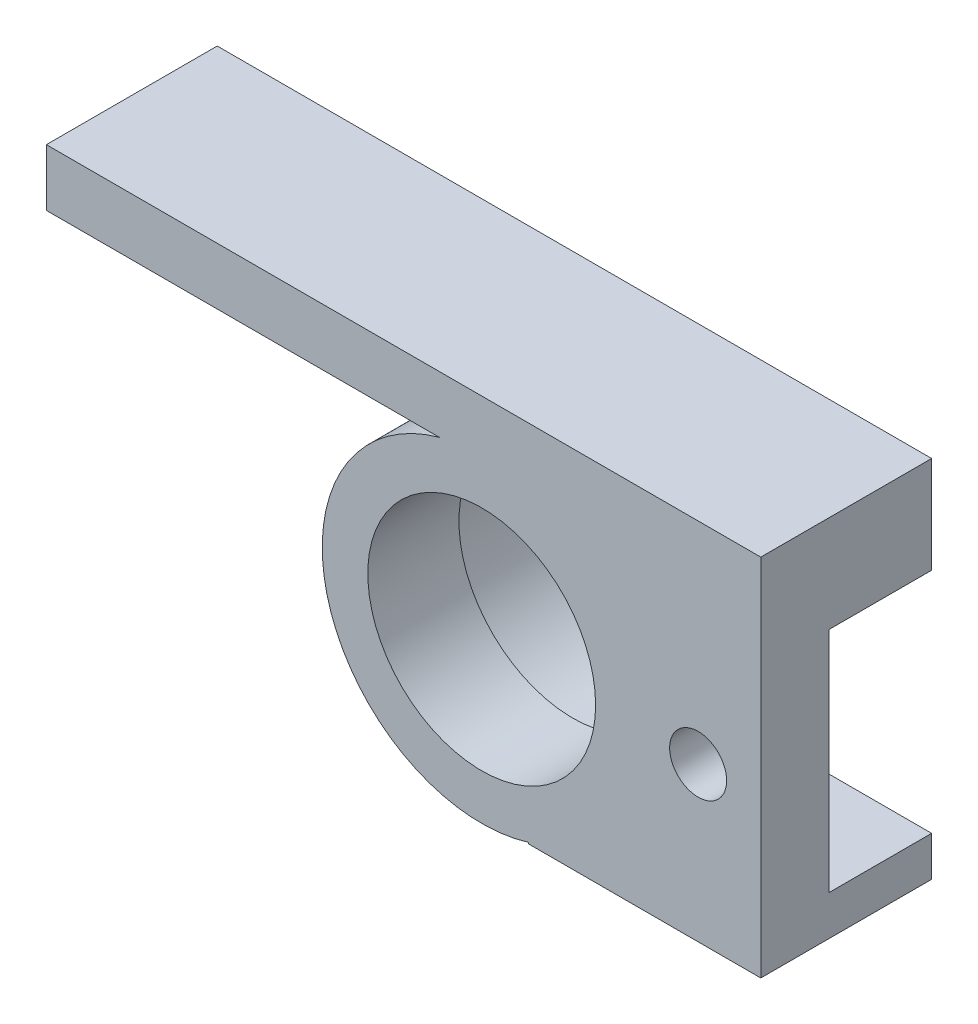
SolidWorks part; units mm, degrees
ref_plane "前视基准面" through (0, 0, 0) normal (0, 0, 1) x (1, 0, 0)
ref_plane "上视基准面" through (0, 0, 0) normal (0, 1, 0) x (1, 0, 0)
ref_plane "右视基准面" through (0, 0, 0) normal (1, 0, 0) x (0, 0, -1)
sketch "草图1" plane through (0, 0, 0) normal (0, 0, 1) x (1, 0, 0)
  line L1 (20, -10) -> (-20, -10)
  line L2 (20, -10) -> (20, 10)
  line L3 (20, 10) -> (-20, 10)
  line L4 (-20, -10) -> (-20, 10)
  line L5 (20, -10) -> (-20, 10) construction
  line L6 (20, 10) -> (-20, -10) construction
  point P0 (0, 0)
  dimension "D1" = 40
  dimension "D2" = 20
extrude "凸台-拉伸1" add sketch "草图1" along normal blind 6
sketch "草图2" plane through (0, 0, 6) normal (0, 0, 1) x (1, 0, 0)
  line L0 (20, -10) -> (20, 10) construction
  circle A0 centre (10, 0) radius 2.5
  circle A1 centre (-1, 0) radius 2.5
  circle A2 centre (-12, 0) radius 2.5
  dimension "D1" = 10
  dimension "D2" = 5
  dimension "D3" = 3
extrude "切除-拉伸1" cut sketch "草图2" against normal through all
sketch "草图3" plane through (0, 0, 6) normal (0, 0, 1) x (1, 0, 0)
  line L0 (20, 13.5) -> (20, 10)
  line L1 (20, -13.5) -> (-26.894, -13.5)
  line L3 (20, 13.5) -> (-26.894, 13.5)
  line L4 (-20, 10) -> (-20, -10)
  line L5 (-20, -10) -> (20, -10)
  line L6 (20, -10) -> (20, 10)
  line L7 (20, 10) -> (-20, 10)
  line L8 (-20, 10) -> (-20, -10)
  line L9 (-20, -10) -> (20, -10)
  line L10 (20, -10) -> (20, 10)
  line L11 (20, 10) -> (-20, 10)
  line L12 (-26.894, -13.5) -> (-26.894, 13.5)
  line L13 (20, -10.0394) -> (-26.894, 13.5) construction
  line L14 (20, 10.0394) -> (-26.894, -13.5) construction
  line L15 (20, -10) -> (20, -13.5)
  circle A0 centre (-31, 0) radius 11
  circle A1 centre (-31, 0) radius 14
  point P2 (0, 0)
  line M10 (-20, 10) -> (-20, -10)
  line M11 (-20, -10) -> (20, -10)
  line M13 (20, 10) -> (-20, 10)
  dimension "D3" = 22
  dimension "D4" = 28
  dimension "D2" = 3.5
  dimension "D1" = 0
extrude "凸台-拉伸2" add sketch "草图3" against normal blind 15 contours L3 A1 L1 L12 A0 | A1 L1 L15 M11 M10 | L1 A1 L8 A0 L12 | L8 A1 L3 L12 A0 | L8 A1 | A1 L0 L3 M10 M13 region at (-1.9449, 11.7771, 6) region at (-1.9449, -11.7771, 6) region at (-23.0173, 9.0328, 6) region at (-27.2274, 11.7946, 6) region at (-18.7882, 0, 6) region at (-23.0173, -9.0328, 6)
sketch "草图5" plane through (0, 0, 6) normal (0, 0, 1) x (1, 0, 0)
  circle A0 centre (-31, 0) radius 10
  circle A1 centre (-31, 0) radius 11 construction
  circle A2 centre (-31, 0) radius 11
  dimension "D1" = 20
extrude "凸台-拉伸3" add sketch "草图5" against normal blind 8
sketch "草图6" plane through (0, 0, 6) normal (0, 0, 1) x (1, 0, 0)
  circle A0 centre (-31, 0) radius 8.5
  circle A1 centre (-31, 0) radius 10 construction
  circle A2 centre (-31, 0) radius 10
  dimension "D1" = 17
sketch "草图7" plane through (0, 13.5, 0) normal (0, 1, 0) x (1, 0, 0)
  circle A0 centre (-17.1666, 1.953) radius 2.6594
sketch "草图8" plane through (20, 0, 0) normal (1, 0, 0) x (0, 0, -1)
  line L1 (-6, 13.5) -> (9, 13.5)
  line L2 (-6, 13.5) -> (-6, 18.5)
  line L3 (-6, 18.5) -> (9, 18.5)
  line L4 (9, 13.5) -> (9, 18.5)
  dimension "D1" = 5
extrude "凸台-拉伸4" add sketch "草图8" against normal blind 500
sketch "草图9" plane through (0, 0, -9) normal (0, 0, -1) x (-1, 0, 0)
  line L1 (24.4567, 15.8334) -> (28.494, 15.8334)
  line L2 (24.4567, 15.8334) -> (24.4567, 12.469)
  line L3 (24.4567, 12.469) -> (28.494, 12.469)
  line L4 (28.494, 15.8334) -> (28.494, 12.469)
extrude "凸台-拉伸5" add sketch "草图9" against normal through all
sketch "草图10" plane through (0, 0, 6) normal (0, 0, 1) x (1, 0, 0)
  line L0 (-12, 0) -> (-1, 0) construction
  line L1 (-6.5, 0) -> (-6.5, 18.5) construction
  line L2 (-480, 18.5) -> (20, 18.5) construction
  line L4 (-6.5, 18.5) -> (20, 18.5)
  line L5 (-6.5, 18.5) -> (-6.5, -13.5)
  line L6 (-6.5, -13.5) -> (20, -13.5)
  line L7 (20, 18.5) -> (20, -13.5)
extrude "切除-拉伸2" cut sketch "草图10" against normal through all
sketch "草图11" plane through (0, 18.5, 0) normal (0, 1, 0) x (1, 0, 0)
  line L0 (-69.2198, 9) -> (-69.2198, -6.0139)
  line L1 (-480, 9) -> (-6.5, 9) construction
  line L2 (-69.2198, 251.4142) -> (-69.2198, -118.5858) construction
sketch "草图12" plane through (0, 18.5, 0) normal (0, 1, 0) x (1, 0, 0)
  line L1 (-69.2198, -6.0139) -> (-501.7351, -6.0139)
  line L2 (-69.2198, -6.0139) -> (-69.2198, 21.5219)
  line L3 (-69.2198, 21.5219) -> (-501.7351, 21.5219)
  line L4 (-501.7351, -6.0139) -> (-501.7351, 21.5219)
extrude "切除-拉伸3" cut sketch "草图12" against normal through all
